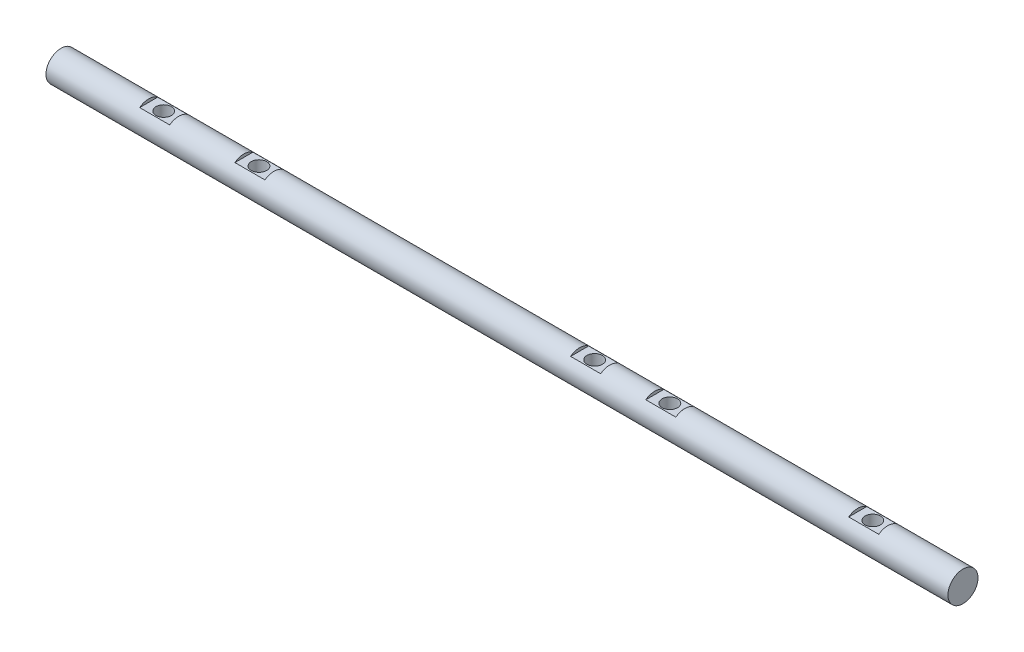
SolidWorks part; units mm, degrees
ref_plane "Front Plane" through (0, 0, 0) normal (0, 0, 1) x (1, 0, 0)
ref_plane "Top Plane" through (0, 0, 0) normal (0, 1, 0) x (1, 0, 0)
ref_plane "Right Plane" through (0, 0, 0) normal (1, 0, 0) x (0, 0, -1)
sketch "Sketch1" plane through (0, 0, 0) normal (1, 0, 0) x (0, 0, -1)
  circle A0 centre (0, 0) radius 3.175
  dimension "D1" = 6.35
extrude "Boss-Extrude1" add sketch "Sketch1" along normal blind 190.5
sketch "Sketch2" plane through (0, 0, 0) normal (0, 1, 0) x (1, 0, 0)
  line L0 (31.75, -3.175) -> (31.75, 3.175)
  line L1 (0, -3.175) -> (190.5, -3.175) construction
  line L2 (190.5, 3.175) -> (0, 3.175) construction
  line L3 (44.9834, 5.3226) -> (38.6334, 5.3226)
  line L4 (18.5166, -5.3226) -> (24.8666, -5.3226)
  line L5 (18.5166, -5.3226) -> (18.5166, 5.3226)
  line L6 (18.5166, 5.3226) -> (24.8666, 5.3226)
  line L7 (24.8666, -5.3226) -> (24.8666, 5.3226)
  line L8 (18.5166, -5.3226) -> (24.8666, 5.3226) construction
  line L9 (18.5166, 5.3226) -> (24.8666, -5.3226) construction
  line L10 (38.6334, -5.3226) -> (38.6334, 5.3226)
  line L11 (44.9834, -5.3226) -> (38.6334, -5.3226)
  line L12 (44.9834, -5.3226) -> (44.9834, 5.3226)
  line L13 (120.65, -3.175) -> (120.65, 3.175)
  line L14 (131.7638, 6.9239) -> (125.4138, 6.9239)
  line L15 (109.5362, -6.9239) -> (115.8862, -6.9239)
  line L16 (109.5362, -6.9239) -> (109.5362, 6.9239)
  line L17 (109.5362, 6.9239) -> (115.8862, 6.9239)
  line L18 (115.8862, -6.9239) -> (115.8862, 6.9239)
  line L19 (109.5362, -6.9239) -> (115.8862, 6.9239) construction
  line L20 (109.5362, 6.9239) -> (115.8862, -6.9239) construction
  line L21 (125.4138, -6.9239) -> (125.4138, 6.9239)
  line L22 (131.7638, -6.9239) -> (125.4138, -6.9239)
  line L23 (131.7638, -6.9239) -> (131.7638, 6.9239)
  line L25 (168.275, -6.1128) -> (174.625, -6.1128)
  line L26 (168.275, -6.1128) -> (168.275, 6.1128)
  line L27 (168.275, 6.1128) -> (174.625, 6.1128)
  line L28 (174.625, -6.1128) -> (174.625, 6.1128)
  line L29 (168.275, -6.1128) -> (174.625, 6.1128) construction
  line L30 (168.275, 6.1128) -> (174.625, -6.1128) construction
  circle A0 centre (21.6916, 0) radius 1.632
  circle A1 centre (41.8084, 0) radius 1.6319
  circle A2 centre (112.7112, 0) radius 1.632
  circle A3 centre (128.5888, 0) radius 1.632
  circle A4 centre (171.45, 0) radius 1.632
  point P35 (120.65, 0)
  point P40 (0, 0)
  dimension "D1" = 31.75
  dimension "D2" = 3.2639
  dimension "D3" = 20.1168
  dimension "D5" = 120.65
  dimension "D6" = 15.8775
  dimension "D8" = 6.35
  dimension "D4" = 6.35
  dimension "D7" = 7.9388
  dimension "D9" = 171.45
  dimension "D10" = 6.35
extrude "Cut-Extrude1" cut sketch "Sketch2" against normal through all both and the other way through all contours A0 | A1 | A3 | A2 | A4 region at (21.6916, 0, 0) region at (41.8084, 0, 0) region at (112.7112, 0, 0) region at (128.5888, 0, 0) region at (171.45, 0, 0)
extrude "Cut-Extrude2" cut sketch "Sketch2<3>" along normal through all from offset 2.54 contours L4 L7 L6 L5 A0 | L11 L12 L3 L10 A1 | L15 L18 L17 L16 A2 | L22 L23 L14 L21 A3 | L26 L25 L28 L27 region at (44.8594, 0, 0) region at (18.6406, 0, 0) region at (131.6114, 0, 0) region at (109.6886, 0, 0)
sketch "Sketch2<3>" plane through (0, 0, 0) normal (0, 1, 0) x (1, 0, 0) same geometry as "Sketch2"
